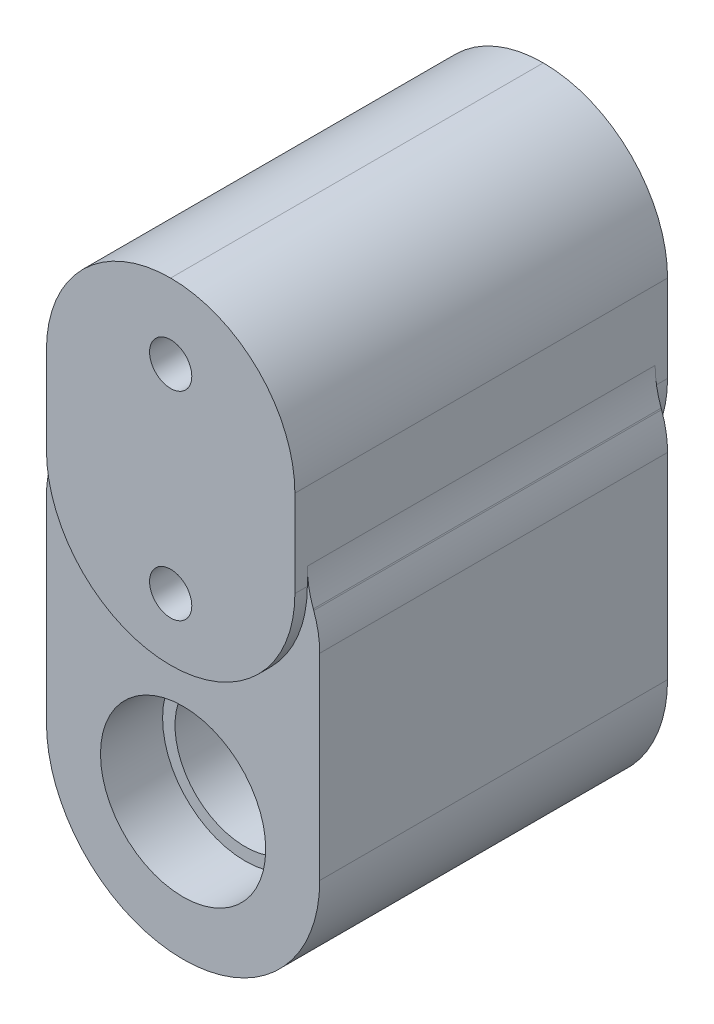
SolidWorks part; units mm, degrees
ref_plane "Спереди" through (0, 0, 0) normal (0, 0, 1) x (1, 0, 0)
ref_plane "Сверху" through (0, 0, 0) normal (0, 1, 0) x (1, 0, 0)
ref_plane "Справа" through (0, 0, 0) normal (1, 0, 0) x (0, 0, -1)
sketch "Эскиз1" plane through (0, 0, 0) normal (0, 0, 1) x (1, 0, 0)
  line L0 (0, 36) -> (0, -11) construction
  line L1 (-11, 37) -> (11, 37)
  line L2 (-11, 37) -> (-11, -11)
  line L3 (-11, -11) -> (11, -11)
  line L4 (11, 37) -> (11, -11)
  line L6 (-11, 0) -> (11, 0) construction
  dimension "D2" = 11
  dimension "D3" = 37
  dimension "D5" = 22
extrude "тело" add sketch "Эскиз1" along normal blind 14 and the other way blind 14
sketch "Эскиз2" plane through (0, 0, 14) normal (0, 0, 1) x (1, 0, 0)
  circle A0 centre (0, 0) radius 6.65
  dimension "D1" = 13.3
extrude "углубление для подшипника" cut sketch "Эскиз2" against normal blind 5
sketch "Эскиз4" plane through (0, 0, 9) normal (0, 0, 1) x (1, 0, 0)
  line L1 (0, 36) -> (0, -11) construction
  line L2 (-11, 0) -> (11, 0) construction
  circle A0 centre (0, 0) radius 5.65
  circle A1 centre (0, 0) radius 6.65 construction
  dimension "D1" = 1
extrude "сквозное отверстие" cut sketch "Эскиз4" against normal through all
mirror "Зеркальное отражение2" about plane through (0, 0, 0) normal (0, 0, 1) of "углубление для подшипника"
fillet "Скругление1" radius 11 2 edges at (11, -11, 0) (-11, -11, 0)
sketch "Эскиз5" plane through (0, 0, -14) normal (0, 0, -1) x (-1, 0, 0)
  line L0 (0, 37) -> (0, -11) construction
  line L1 (-11, 37) -> (11, 37) construction
  circle A0 centre (0, 31) radius 1.7
  circle A1 centre (0, 15) radius 1.7
  circle A2 centre (0, 0) radius 6.65 construction
  dimension "D1" = 3.4
  dimension "D2" = 16
  dimension "D3" = 15
extrude "отверстия для шурупов" cut sketch "Эскиз5" against normal through all
sketch "Эскиз9" plane through (0, 0, 14) normal (0, 0, 1) x (1, 0, 0)
  line L1 (-11, 10) -> (11, 10) construction
  line L2 (-10, 37) -> (10, 37)
  line L4 (-11, 37) -> (-11, 0) construction
  line L5 (11, 0) -> (11, 37) construction
  line L6 (-10, 20) -> (-10, 37)
  line L9 (10, 37) -> (10, 20)
  line L10 (11, 37) -> (-11, 37) construction
  arc A0 (-10, 20) -> (10, 20) centre (0, 20) ccw
  circle A1 centre (0, 15) radius 1.7
  circle A2 centre (0, 31) radius 1.7
  circle A3 centre (0, 31) radius 1.7 construction
  circle A5 centre (0, 15) radius 1.7 construction
  point P23 (0, 37)
  dimension "D1" = 10
  dimension "D2" = 5
  dimension "D3" = 20
extrude "выступы" add sketch "Эскиз9" along normal blind 1
mirror "Зеркальное отражение1" about plane through (0, 0, 0) normal (0, 0, 1) of "выступы"
sketch "Эскиз10" plane through (0, 0, 14) normal (0, 0, 1) x (1, 0, 0)
  line L0 (-10, 37) -> (-11, 37)
  line L1 (-11, 37) -> (-11, 17.2525)
  line L2 (-11, 37) -> (-11, 0) construction
  line L3 (0, 37) -> (0, 15) construction
  line L4 (-10, 37) -> (-10, 20)
  line L5 (-11, 17.2525) -> (-10, 20)
  line L6 (10, 37) -> (-10, 37) construction
  line L7 (11, 17.2525) -> (10, 20)
  line L8 (10, 37) -> (10, 20)
  line L9 (11, 37) -> (11, 17.2525)
  line L10 (10, 37) -> (11, 37)
  dimension "D1" = 20
extrude "Сглаживание перехода" cut sketch "Эскиз10" against normal up to next
fillet "Скругление2" radius 8 4 edges at (10, 20, 0) (11, 17.2525, 0) (-10, 20, 0) (-11, 17.2525, 0)
fillet "Скругление3" radius 10 2 edges at (-10, 37, 0) (10, 37, 0)
